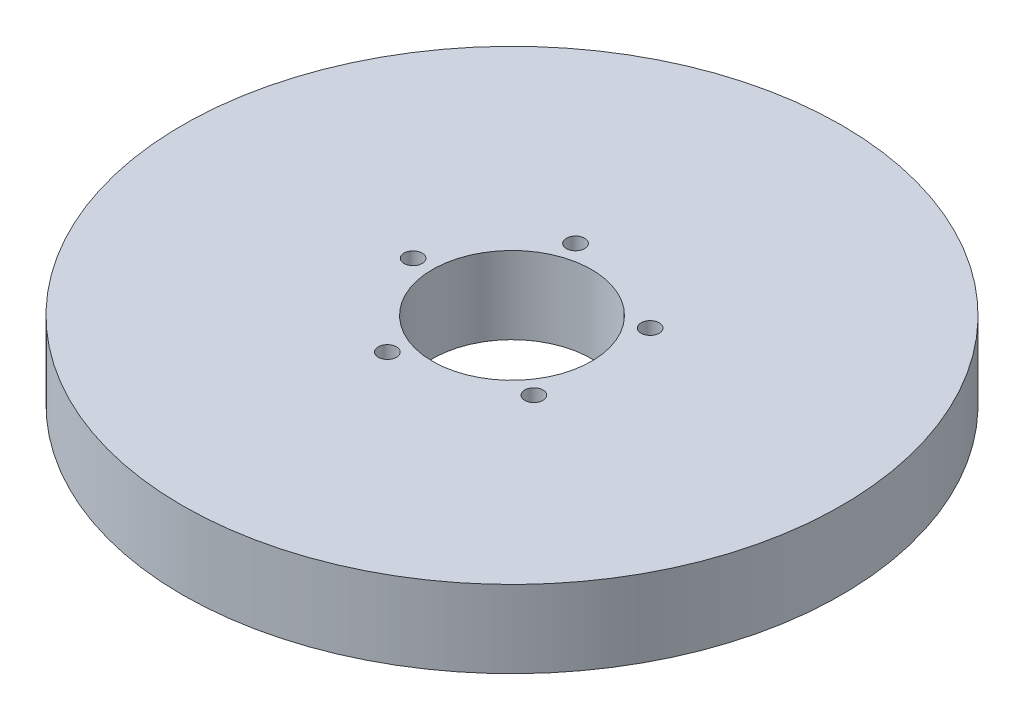
SolidWorks part; units mm, degrees
ref_plane "Front Plane" through (0, 0, 0) normal (0, 0, 1) x (1, 0, 0)
ref_plane "Top Plane" through (0, 0, 0) normal (0, 1, 0) x (1, 0, 0)
ref_plane "Right Plane" through (0, 0, 0) normal (1, 0, 0) x (0, 0, -1)
sketch "Sketch1" plane through (0, 0, 0) normal (0, 1, 0) x (1, 0, 0)
  circle A0 centre (0, 0) radius 72.5
  dimension "FLANGE_OD" = 145
extrude "Boss-Extrude1" add sketch "Sketch1" along normal blind 17
sketch "Sketch2" plane through (0, 0, 0) normal (0, 1, 0) x (1, 0, 0)
  circle A0 centre (0, 0) radius 17.5
  dimension "BORE_D" = 35
extrude "Cut-Extrude1" cut sketch "Sketch2" along normal through all
sketch "Sketch3" plane through (0, 17, 0) normal (0, 1, 0) x (1, 0, 0)
  circle A0 centre (0, 0) radius 21.7632 construction
  circle A1 centre (-21.7632, 0) radius 1.9978
  dimension "BOLT_D" = 3.9957
  dimension "BOLT_PCD" = 43.5263
extrude "Cut-Extrude2" cut sketch "Sketch3" against normal blind 12.1475
pattern_circular "CirPattern1" count 5 over 360 about axis through (0, 0, 0) along (0, 1, 0) of "Cut-Extrude2"
